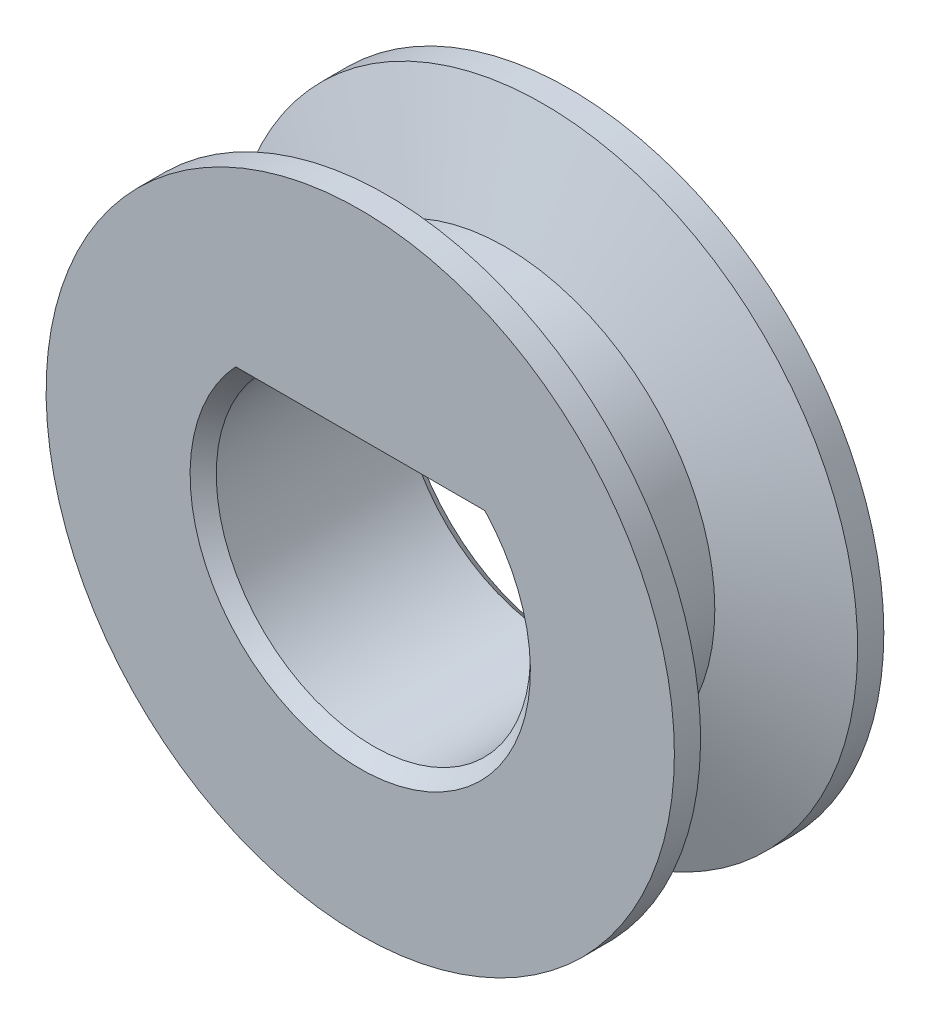
SolidWorks part; units mm, degrees
material "6061-T6 (SS)"
ref_plane "Front Plane" through (0, 0, 0) normal (0, 0, 1) x (1, 0, 0)
ref_plane "Top Plane" through (0, 0, 0) normal (0, 1, 0) x (1, 0, 0)
ref_plane "Right Plane" through (0, 0, 0) normal (1, 0, 0) x (0, 0, -1)
sketch "Sketch1" plane through (0, 0, 0) normal (0, 0, 1) x (1, 0, 0)
  circle A0 centre (0, 0) radius 19.05
  circle A1 centre (0, 0) radius 9.525
  dimension "D1" = 38.1
  dimension "D2" = 19.05
extrude "Extrude1" add sketch "Sketch1" along normal mid plane 12.7
sketch "Sketch2" plane through (0, 0, 0) normal (1, 0, 0) x (0, 0, -1)
  line L0 (-4.7625, 19.05) -> (4.7625, 19.05)
  line L2 (4.7625, 19.05) -> (2.4513, 12.7)
  line L3 (2.4513, 12.7) -> (-2.4513, 12.7)
  line L4 (-2.4513, 12.7) -> (-4.7625, 19.05)
  line L5 (-6.35, 0) -> (6.35, 0) construction
  line L6 (-6.35, 19.05) -> (-6.35, -19.05) construction
  line L7 (6.35, -19.05) -> (6.35, 19.05) construction
  point P2 (0, 19.05)
  point P5 (0, 12.7)
  dimension "D1" = 19.05
  dimension "D2" = 6.35
  dimension "D3" = 9.525
  dimension "D4" = 40
chamfer "Chamfer1" distance 0.7937 angle 45 2 edges at (9.525, 0, -6.35) (9.525, 0, 6.35)
revolve "Cut-Revolve1" cut sketch "Sketch2" angle 360 about L5
sketch "Sketch3" plane through (0, 0, -6.35) normal (0, 0, -1) x (-1, 0, 0)
  line L0 (0, 0) -> (0, 9.525) construction
  line L5 (-7.5582, 7.025) -> (7.5582, 7.025)
  circle A1 centre (0, 0) radius 10.3188 construction
  circle A2 centre (0, 0) radius 9.525 construction
  arc A3 (-7.5582, 7.025) -> (7.5582, 7.025) centre (0, 0) cw
  circle M6 centre (0, 0) radius 10.3188
  dimension "D1" = 2.5
extrude "Boss-Extrude1" add sketch "Sketch3" against normal through all contours L5 M6 region at (0, 8.3624, -6.35)
